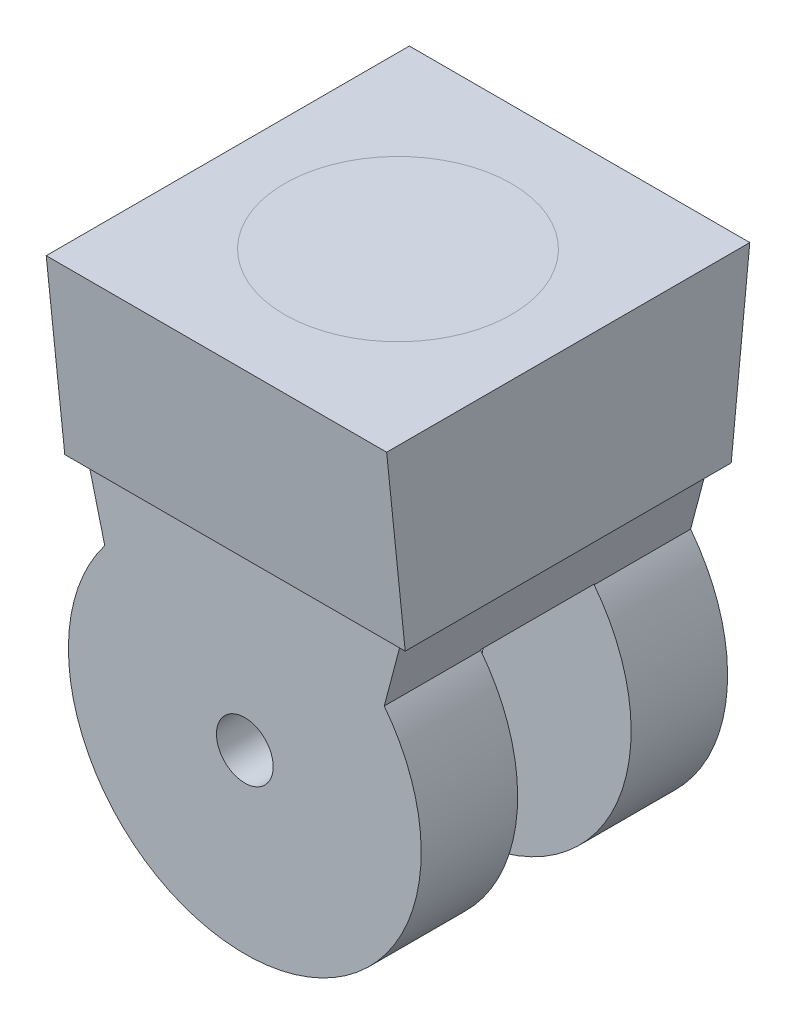
SolidWorks part; units mm, degrees
ref_plane "Alzado" through (0, 0, 0) normal (0, 0, 1) x (1, 0, 0)
ref_plane "Planta" through (0, 0, 0) normal (0, 1, 0) x (1, 0, 0)
ref_plane "Vista lateral" through (0, 0, 0) normal (1, 0, 0) x (0, 0, -1)
sketch "Croquis1" plane through (0, 0, 0) normal (1, 0, 0) x (0, 0, -1)
  line L0 (-40.64, 20.32) -> (-36.4861, -20.32)
  line L1 (-36.4861, -20.32) -> (0, -20.32)
  line L2 (40.64, 20.32) -> (36.4861, -20.32)
  line L3 (36.4861, -20.32) -> (0, -20.32)
  line L4 (-40.64, 20.32) -> (40.64, 20.32)
  line L5 (0, 20.32) -> (0, 0) construction
  line L6 (0, 0) -> (0, -20.32) construction
  dimension "D1" = 36.4861
  dimension "D2" = 36.4861
  dimension "D3" = 40.64
  dimension "D4" = 40.64
extrude "Saliente-Extruir1" add sketch "Croquis1" along normal mid plane 76.2
sketch "Croquis2" plane through (0, 0, 0) normal (0, 0, 1) x (1, 0, 0)
  line L0 (35.2237, -20.32) -> (31.2096, -35.5067)
  line L1 (38.1, -20.32) -> (-38.1, -20.32) construction
  line L2 (0, 34.8542) -> (0, -59.69) construction
  line L3 (-35.2237, -20.32) -> (35.2237, -20.32)
  line L4 (-35.2237, -20.32) -> (-31.3489, -35.6876)
  arc A0 (-31.3489, -35.6876) -> (31.2096, -35.5067) centre (0, -59.69) ccw
  dimension "D1" = 39.37
extrude "Saliente-Extruir2" add sketch "Croquis2" along normal mid plane 68.58
sketch "Croquis3" plane through (0, 0, 0) normal (0, 0, 1) x (1, 0, 0)
  circle A0 centre (0, -59.69) radius 39.6588
  dimension "D1" = 79.3175
extrude "Cortar-Extruir1" cut sketch "Croquis3" against normal mid plane 25.4
sketch "Croquis4" plane through (0, 0, 34.29) normal (0, 0, 1) x (1, 0, 0)
  circle A0 centre (0, -59.69) radius 6.35
  dimension "D1" = 12.7
extrude "Cortar-Extruir2" cut sketch "Croquis4" against normal through all
sketch "Croquis8" plane through (0, 20.32, 0) normal (0, 1, 0) x (1, 0, 0)
  circle A0 centre (0, 0) radius 25.4
  dimension "D1" = 50.8
split line "Línea de partición1"
ref_axis "joint4" through (0, -105.6354, 0) along (0, 1, 0)
ref_axis "joint5" through (0, -59.69, -34.29) along (0, 0, 1)
ref_point "Link456_Refe"
